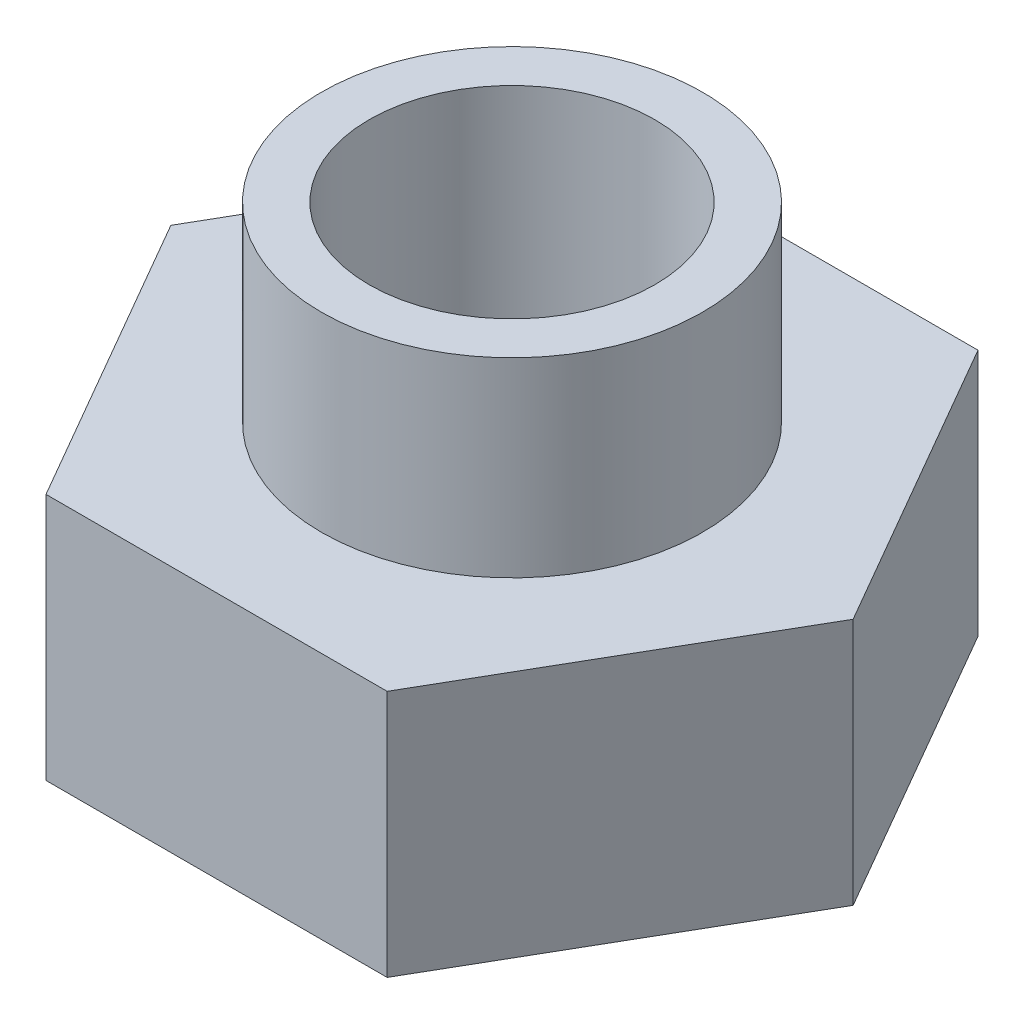
SolidWorks part; units mm, degrees
ref_plane "Front Plane" through (0, 0, 0) normal (0, 0, 1) x (1, 0, 0)
ref_plane "Top Plane" through (0, 0, 0) normal (0, 1, 0) x (1, 0, 0)
ref_plane "Right Plane" through (0, 0, 0) normal (1, 0, 0) x (0, 0, -1)
sketch "Sketch1" plane through (0, 0, 0) normal (0, 1, 0) x (1, 0, 0)
  line L0 (0, 130.2184) -> (0, -131.3657) construction
  line L1 (-176.3016, 0) -> (192.7462, 0) construction
  line L3 (89.4893, 0) -> (44.7446, 77.5)
  line L4 (44.7446, 77.5) -> (-44.7446, 77.5)
  line L5 (-44.7446, 77.5) -> (-89.4893, 0)
  line L6 (-89.4893, 0) -> (-44.7446, -77.5)
  line L7 (-44.7446, -77.5) -> (44.7446, -77.5)
  line L8 (44.7446, -77.5) -> (89.4893, 0)
  circle A0 centre (0, 0) radius 77.5 construction
  circle A1 centre (0, 0) radius 37.5
  circle A2 centre (0, 0) radius 50
  point P15 (0, 0)
  dimension "D2" = 100
  dimension "D3" = 75
  dimension "D1" = 155
extrude "Boss-Extrude1" add sketch "Sketch1" along normal blind 65 contours L7 L8 L3 L4 L5 L6 A2 region at (65.0665, 0, 37.5662)
extrude "Boss-Extrude2" add sketch "Sketch1<3>" along normal blind 115 contours A2
sketch "Sketch1<3>" plane through (0, 0, 0) normal (0, 1, 0) x (1, 0, 0) same geometry as "Sketch1"
extrude "Cut-Extrude1" cut sketch "Sketch1<4>" along normal blind 115 contours A1
sketch "Sketch1<4>" plane through (0, 0, 0) normal (0, 1, 0) x (1, 0, 0) same geometry as "Sketch1"
